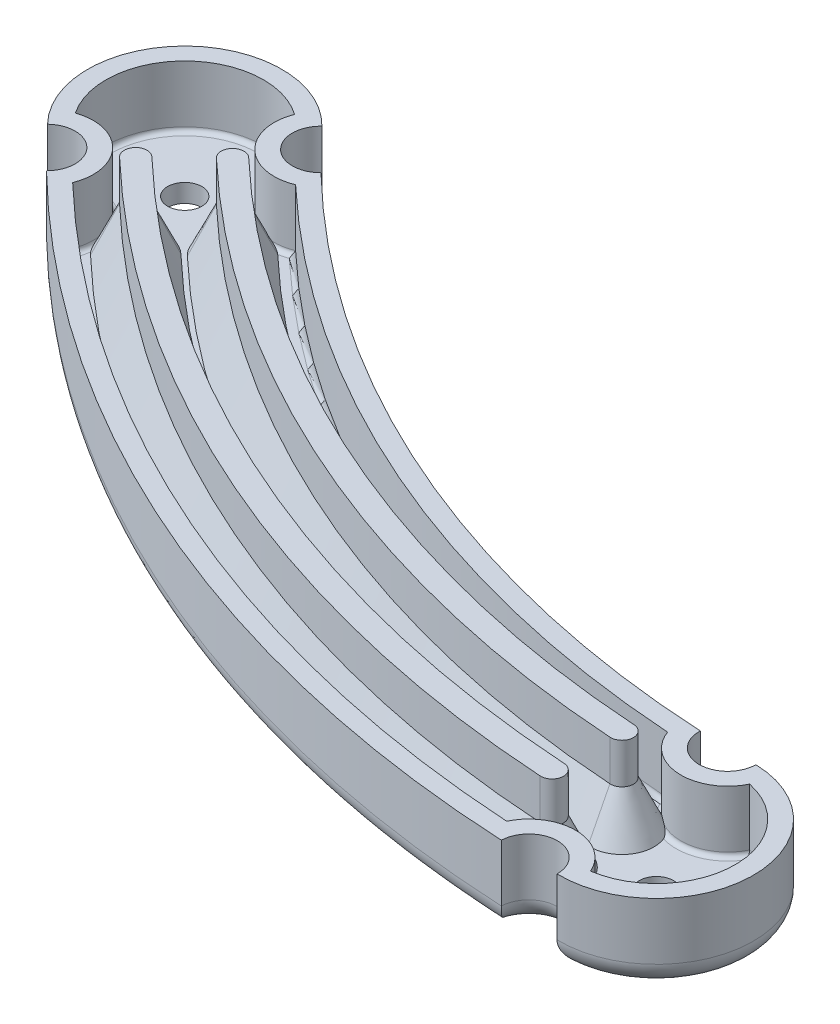
SolidWorks part; units mm, degrees
ref_plane "Front Plane" through (0, 0, 0) normal (0, 0, 1) x (1, 0, 0)
ref_plane "Top Plane" through (0, 0, 0) normal (0, 1, 0) x (1, 0, 0)
ref_plane "Right Plane" through (0, 0, 0) normal (1, 0, 0) x (0, 0, -1)
sketch "Sketch1" plane through (0, 0, 0) normal (0, 1, 0) x (1, 0, 0)
  line L0 (-71.3503, -82.2054) -> (-34958.9124, 35734.8019) construction
  line L1 (-70.1201, -59.1107) -> (-34995.8073, 35720.7213) construction
  line L2 (-39.7979, -107.5277) -> (49945.2079, -1331.9458) construction
  line L3 (31.7139, -92.3079) -> (50015.3873, -1369.9589) construction
  circle A0 centre (0, 0) radius 100 construction
  arc A1 (-0.2082, -108.4975) -> (0.2172, -91.5028) centre (0, -100) ccw
  arc A2 (-67.2386, -62.0626) -> (-79.4101, -73.9309) centre (-73.3212, -68) ccw
  arc A3 (-63.7464, -65.6403) -> (-4.7807, -91.375) centre (0, 0) ccw
  arc A4 (-75.9216, -77.5123) -> (-5.2063, -108.375) centre (0, 0) ccw
  arc A5 (-67.2386, -62.0626) -> (-63.7464, -65.6403) centre (-65.5159, -63.8743) ccw
  arc A6 (-75.9216, -77.5123) -> (-79.4101, -73.9309) centre (-77.6873, -75.7425) ccw
  arc A7 (-4.7807, -91.375) -> (0.2172, -91.5028) centre (-2.2826, -91.4715) ccw
  arc A8 (-0.2082, -108.4975) -> (-5.2063, -108.375) centre (-2.708, -108.4662) ccw
  dimension "D1" = 200
  dimension "D3" = 17
  dimension "D4" = 5
  dimension "D2" = 80
extrude "Boss-Extrude1" add sketch "Sketch1" along normal blind 7
fillet "Fillet1" radius 2 8 edges at (8.4973, 0, 100.2127) (-2.3465, 0, 93.9707) (-36.6, 0, 83.8611) (-67.3049, 0, 65.6206) (-79.2553, 0, 61.9143) (-75.8965, 0, 73.9981) (-43.4, 0, 99.4419) (-2.6467, 0, 105.967)
shell "Shell1" thickness 1.6 removed face at (-37.3691, 7, 85.6233)
sketch "Sketch2" plane through (0, 1.6, 0) normal (0, 1, 0) x (1, 0, 0)
  line L0 (-73.8794, -77.2622) -> (-63.9482, -67.6627) construction
  line L1 (-6.1264, -92.8982) -> (-6.4116, -106.7075) construction
  arc A0 (-66.7567, -70.3775) -> (-6.207, -96.8035) centre (0, 0) ccw construction
  arc A1 (-71.0708, -74.5475) -> (-6.331, -102.8022) centre (0, 0) ccw construction
  arc A2 (-71.7608, -75.2712) -> (-6.3924, -103.8003) centre (0, 0) ccw
  arc A3 (-67.4449, -71.103) -> (-6.271, -97.8015) centre (0, 0) ccw
  arc A4 (-70.3808, -73.8237) -> (-6.2695, -101.8041) centre (0, 0) ccw
  arc A5 (-66.0685, -69.6519) -> (-6.1431, -95.8056) centre (0, 0) ccw
  arc A6 (-71.7608, -75.2712) -> (-70.3808, -73.8237) centre (-71.0708, -74.5475) cw
  arc A7 (-6.3924, -103.8003) -> (-6.2695, -101.8041) centre (-6.331, -102.8022) ccw
  arc A8 (-67.4449, -71.103) -> (-66.0685, -69.6519) centre (-66.7567, -70.3775) cw
  arc A9 (-6.271, -97.8015) -> (-6.1431, -95.8056) centre (-6.207, -96.8035) ccw
  point P12 (-66.7567, -70.3775)
  point P13 (-71.0708, -74.5475)
  point P14 (-68.9138, -72.4625)
  dimension "D1" = 3
  dimension "D2" = 3
  dimension "D3" = 1
  dimension "D4" = 1
extrude "Boss-Extrude2" add sketch "Sketch2" along normal offset from surface (7.4 mm away) 2 up to face at (-37.4353, 7, 85.775) offset beyond the face yes
chamfer "Chamfer1" distance 1.8 angle 65 8 edges at (-38.4009, 1.6, 87.9876) (-67.4822, 1.6, 69.6893) (-5.2091, 1.6, 96.8675) (-39.2009, 1.6, 89.8206) (-40.7988, 1.6, 93.4818) (-71.7946, 1.6, 73.8574) (-5.3328, 1.6, 102.8637) (-41.5988, 1.6, 95.3148) first distance on face at (-37.4529, 1.6, 85.8155)
sketch "Sketch3" plane through (0, 0, 0) normal (0, -1, 0) x (-1, 0, 0)
  circle A0 centre (73.3212, -68) radius 1.5
  circle A1 centre (0, -100) radius 1.5
  dimension "D1" = 3
extrude "Cut-Extrude1" cut sketch "Sketch3" against normal through all
